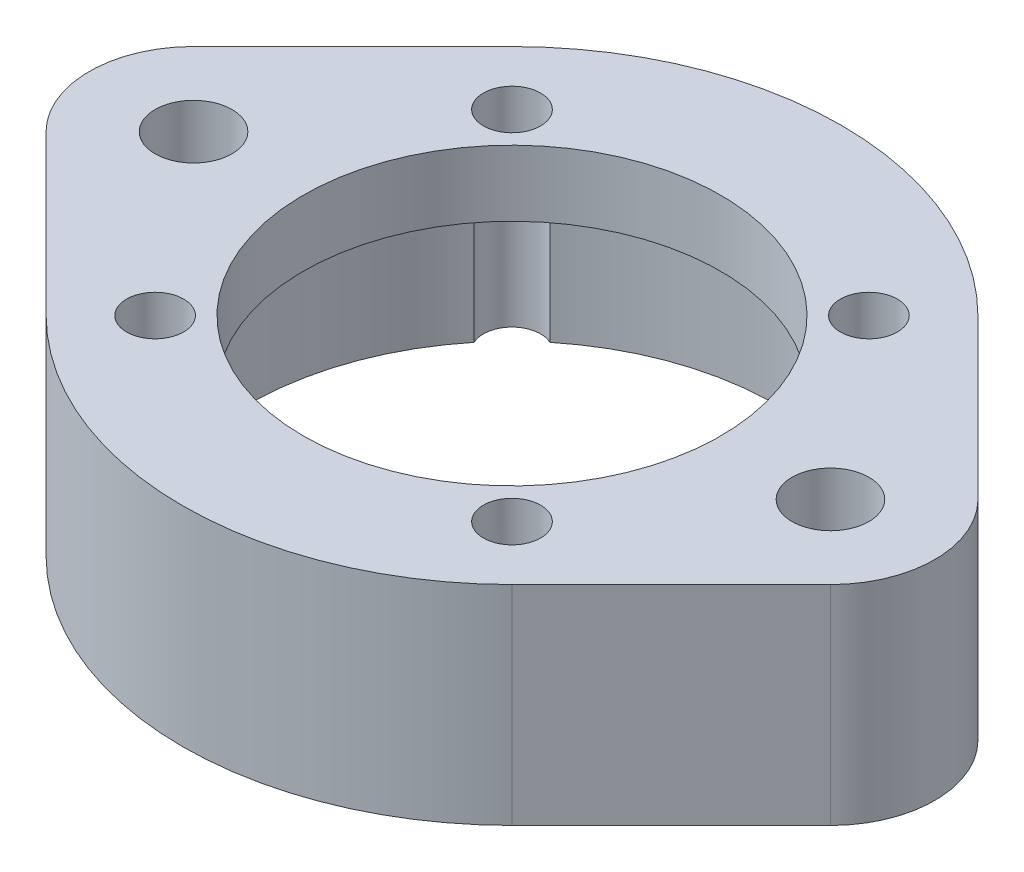
SolidWorks part; units mm, degrees
material "ABS"
ref_plane "Front Plane" through (0, 0, 0) normal (0, 0, 1) x (1, 0, 0)
ref_plane "Top Plane" through (0, 0, 0) normal (0, 1, 0) x (1, 0, 0)
ref_plane "Right Plane" through (0, 0, 0) normal (1, 0, 0) x (0, 0, -1)
sketch "Sketch1" plane through (0, 0, 0) normal (0, 1, 0) x (1, 0, 0)
  line L0 (0, 15) -> (0, -15) construction
  line L1 (-17.8578, 3.3598) -> (-10.6034, 10.6098)
  line L2 (0, 0) -> (-14.5, 0) construction
  line L3 (-17.8578, -3.3598) -> (-10.6034, -10.6098)
  line L4 (17.8578, 3.3598) -> (10.6034, 10.6098)
  line L5 (17.8578, -3.3598) -> (10.6034, -10.6098)
  arc A0 (-10.6034, -10.6098) -> (10.6034, -10.6098) centre (0, 0) ccw
  circle A1 centre (0, 0) radius 12
  circle A2 centre (-14.5, 0) radius 1.75
  arc A3 (-17.8578, 3.3598) -> (-17.8578, -3.3598) centre (-14.5, 0) ccw
  circle A4 centre (14.5, 0) radius 1.75
  arc A5 (17.8578, 3.3598) -> (17.8578, -3.3598) centre (14.5, 0) cw
  arc A6 (10.6034, 10.6098) -> (-10.6034, 10.6098) centre (0, 0) ccw
  point P25 (0, 0)
  dimension "D1" = 30
  dimension "D2" = 24
  dimension "D3" = 3.5
  dimension "D4" = 14.5
  dimension "D5" = 3
extrude "Boss-Extrude1" add sketch "Sketch1" along normal blind 9.5
sketch "Sketch3" plane through (0, 9.5, 0) normal (0, 1, 0) x (1, 0, 0)
  circle A0 centre (0, 0) radius 12 construction
  circle A1 centre (0, 0) radius 12
  circle A2 centre (0, 0) radius 9.5
  dimension "D1" = 19
extrude "Boss-Extrude2" add sketch "Sketch3" against normal blind 3
sketch "Sketch4" plane through (0, 9.5, 0) normal (0, 1, 0) x (1, 0, 0)
  line L1 (8.125, -8.125) -> (-8.125, -8.125) construction
  line L2 (8.125, -8.125) -> (8.125, 8.125) construction
  line L3 (8.125, 8.125) -> (-8.125, 8.125) construction
  line L4 (-8.125, -8.125) -> (-8.125, 8.125) construction
  line L5 (8.125, -8.125) -> (-8.125, 8.125) construction
  line L6 (8.125, 8.125) -> (-8.125, -8.125) construction
  circle A0 centre (8.125, 8.125) radius 1.3
  circle A1 centre (-8.125, 8.125) radius 1.3
  circle A2 centre (-8.125, -8.125) radius 1.3
  circle A3 centre (8.125, -8.125) radius 1.3
  point P0 (0, 0)
  dimension "D1" = 2.6
  dimension "D2" = 16.25
extrude "Cut-Extrude1" cut sketch "Sketch4" against normal through all
